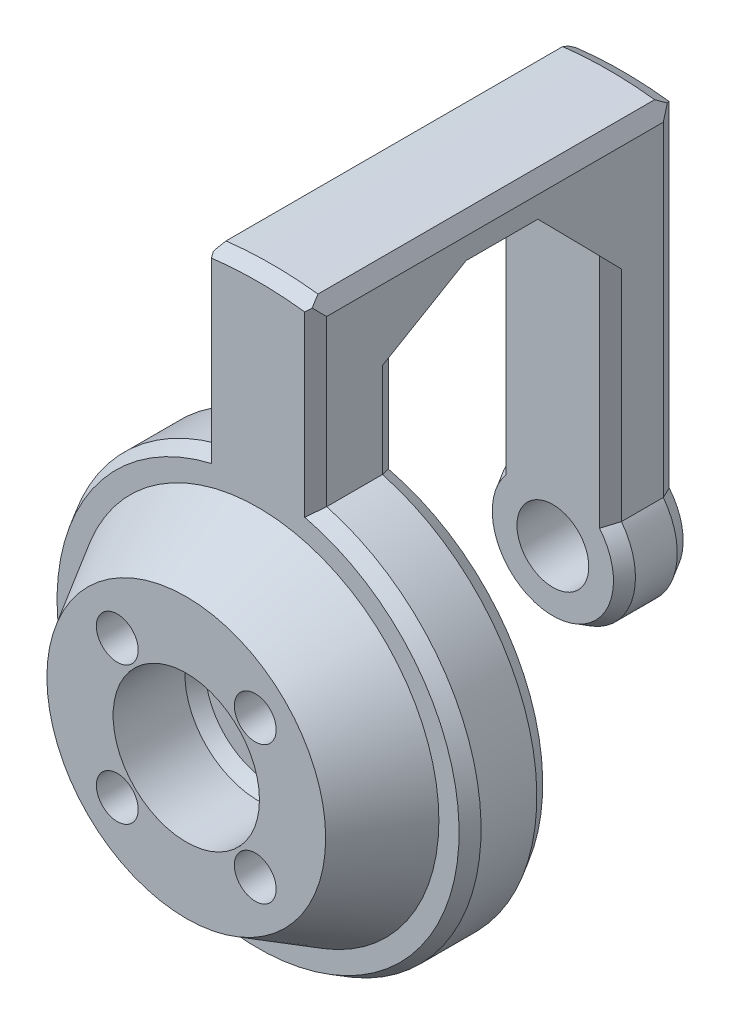
SolidWorks part; units mm, degrees
ref_plane "Plan de face" through (0, 0, 0) normal (0, 0, 1) x (1, 0, 0)
ref_plane "Plan de dessus" through (0, 0, 0) normal (0, 1, 0) x (1, 0, 0)
ref_plane "Plan de droite" through (0, 0, 0) normal (1, 0, 0) x (0, 0, -1)
sketch "Esquisse1" plane through (0, 0, 0) normal (0, 0, 1) x (1, 0, 0)
  line L0 (-3.925, 0) -> (3.925, 0)
  line L1 (-3.925, 0) -> (-3.925, 27.2942)
  line L2 (3.925, 0) -> (3.925, 27.2942)
  circle A0 centre (0, 0) radius 15
  circle A1 centre (0, 0) radius 2.575
  arc A2 (3.925, 27.2942) -> (-3.925, 27.2942) centre (0, 0) ccw
  arc A3 (-3.925, 27.2942) -> (3.925, 27.2942) centre (0, 0) ccw construction
  point P7 (0, 0)
  dimension "D1" = 30
  dimension "D2" = 5.15
  dimension "D3" = 55.15
  dimension "D4" = 7.85
extrude "Boss.-Extru.1" add sketch "Esquisse1" along normal blind 6 contours A1 L0 L1 A0 L2 | A1 L0 L2 A0 L1 | L2 A2 L1 A0 region at (0, 8.0356, 0) region at (3.25, -0.4206, 0) region at (0, 21.1536, 0)
sketch "Esquisse2" plane through (0, 0, 0) normal (0, 0, -1) x (-1, 0, 0)
  line L5 (-3.925, 27.2942) -> (-3.925, 24.7659)
  line L7 (-3.925, 14.4774) -> (-3.925, 27.2942) construction
  line L9 (3.925, 27.2942) -> (3.925, 24.7659)
  line L10 (3.925, 14.4774) -> (3.925, 27.2942) construction
  arc A6 (3.925, 27.2942) -> (-3.925, 27.2942) centre (0, 0) ccw
  arc A7 (3.925, 24.7659) -> (-3.925, 24.7659) centre (0, 0) ccw
  arc A8 (3.925, 27.2942) -> (-3.925, 27.2942) centre (0, 0) ccw construction
  arc A9 (-3.925, 24.7659) -> (3.925, 24.7659) centre (0, 0) ccw construction
  arc A10 (-3.925, 27.2942) -> (3.925, 27.2942) centre (0, 0) ccw construction
  dimension "D1" = 50.15
extrude "Boss.-Extru.2" add sketch "Esquisse2" along normal blind 15.15
sketch "Esquisse3" plane through (0, 0, -15.15) normal (0, 0, -1) x (-1, 0, 0)
  line L0 (0, -10.3999) -> (0, 10.3999) construction
  line L3 (-3.925, 0) -> (3.925, 0)
  line L5 (-3.925, 27.2942) -> (-3.925, 0)
  line L7 (-3.925, 27.2942) -> (-3.925, 24.7659) construction
  line L8 (3.925, 27.2942) -> (3.925, 0)
  arc A3 (3.925, 27.2942) -> (-3.925, 27.2942) centre (0, 0) ccw
  arc A4 (3.925, 27.2942) -> (-3.925, 27.2942) centre (0, 0) ccw construction
  circle A5 centre (0, 0) radius 4.925
  arc A6 (-3.925, 27.2942) -> (0, -27.575) centre (0, 0) ccw construction
  arc A7 (0, -27.575) -> (3.925, 27.2942) centre (0, 0) ccw construction
  point P4 (0, 0)
  point P13 (0, 0)
  dimension "D1" = 9.85
extrude "Boss.-Extru.3" add sketch "Esquisse3" along normal blind 5 contours A3 L5 L3 L8 | A5
sketch "Esquisse4" plane through (0, 0, 6) normal (0, 0, 1) x (1, 0, 0)
  circle A0 centre (0, 0) radius 10
  dimension "D1" = 20
extrude "Boss.-Extru.4" add sketch "Esquisse4" along normal blind 5.15
sketch "Esquisse5" plane through (0, 0, 0) normal (0, 0, -1) x (-1, 0, 0)
  circle A0 centre (0, 0) radius 10
  dimension "D1" = 20
extrude "Enlèv. mat.-Extru.2" cut sketch "Esquisse5" against normal blind 3
sketch "Esquisse6" plane through (0, 0, 6) normal (0, 0, 1) x (1, 0, 0)
  circle A0 centre (0, 0) radius 5.25
  dimension "D1" = 10.5
extrude "Enlèv. mat.-Extru.3" cut sketch "Esquisse6" along normal through all and the other way blind 1
sketch "Esquisse7" plane through (0, 0, 6) normal (0, 0, 1) x (1, 0, 0)
  circle A0 centre (-4.9497, -4.9497) radius 1.5
  circle A1 centre (4.9497, -4.9497) radius 1.5
  circle A2 centre (4.9497, 4.9497) radius 1.5
  circle A3 centre (-4.9497, 4.9497) radius 1.5
  dimension "D1" = 3
extrude "Enlèv. mat.-Extru.4" cut sketch "Esquisse7" along direction (0, 0, -1) on the side against the normal mid plane 11
sketch "Esquisse8" plane through (0, 0, 0) normal (0, 0, 1) x (1, 0, 0)
  circle A0 centre (0, 0) radius 2.575
  circle A1 centre (0, 0) radius 2.575 construction
extrude "Enlèv. mat.-Extru.1" cut sketch "Esquisse8" against normal through all both and the other way through all
chamfer "Chanfrein1" distance 5.15 angle 30 1 edges at (10, 0, 6) first distance on face at (10, 0, 11.15)
chamfer "Chanfrein2" distance 2.5 angle 30 1 edges at (-10, 0, 3) first distance on face at (-10, 0, 3)
chamfer "Chanfrein3" distance 1 angle 25 1 edges at (5.25, 0, 5) first distance on face at (5.25, 0, 5)
chamfer "Chanfrein4" distance 5 angle 30 1 edges at (0, 25.075, 0) first distance on face at (0, 24.9205, -7.575)
chamfer "Chanfrein5" distance 5 angle 45 1 edges at (0, 25.075, -15.15)
chamfer "Chanfrein6" distance 1 angle 30 3 edges at (3.925, 18.1579, 0) (-3.925, 18.1579, 0) (0, -15, 0) first distance on face at (3.925, 18.1626, -6.875) first distance on face at (-3.925, 17.9475, -7.875) first distance on face at (0, -0.2613, 3)
chamfer "Chanfrein7" distance 1 angle 30 3 edges at (3.925, 11.3312, -15.15) (-3.925, 11.3312, -15.15) (0, -4.925, -15.15) first distance on face at (3.925, 18.1333, -6.725) first distance on face at (-3.925, 17.6254, -7.225) first distance on face at (0, -0.9751, -17.65)
chamfer "Chanfrein8" distance 1 angle 30 4 edges at (3.925, 15.1346, -20.15) (3.925, 27.2942, -7.075) (0, -15, 6) (3.925, 20.8858, 6) first distance on face at (3.925, 17.5744, -7.375) first distance on face at (0, -0.2613, 3.5)
chamfer "Chanfrein9" distance 1 angle 30 4 edges at (-3.925, 27.2942, -7.075) (-3.925, 15.1346, -20.15) (0.43, -4.9062, -20.15) (-3.925, 20.5863, 6) first distance on face at (-3.925, 17.2656, -6.2955) first distance on face at (0.8161, -0.115, -18.3452)
sketch "Esquisse9" plane through (0, 0, 3) normal (0, 0, -1) x (-1, 0, 0)
  circle A0 centre (4.9497, -4.9497) radius 2.575
  circle A1 centre (-4.9497, -4.9497) radius 2.575
  circle A2 centre (-4.9497, 4.9497) radius 2.575
  circle A3 centre (4.9497, 4.9497) radius 2.575
  dimension "D1" = 5.15
extrude "Enlèv. mat.-Extru.5" cut sketch "Esquisse9" along normal up to surface (3 mm away) and the other way blind 0.5 up to face at (0, 10.9322, 0)
chamfer "Chanfrein10" distance 1 angle 30 1 edges at (0, 27.575, 6) first distance on face at (0, 27.4759, -7.075)
chamfer "Chanfrein11" distance 1 angle 30 1 edges at (0, 27.575, -20.15) first distance on face at (0, 27.4759, -7.575)
